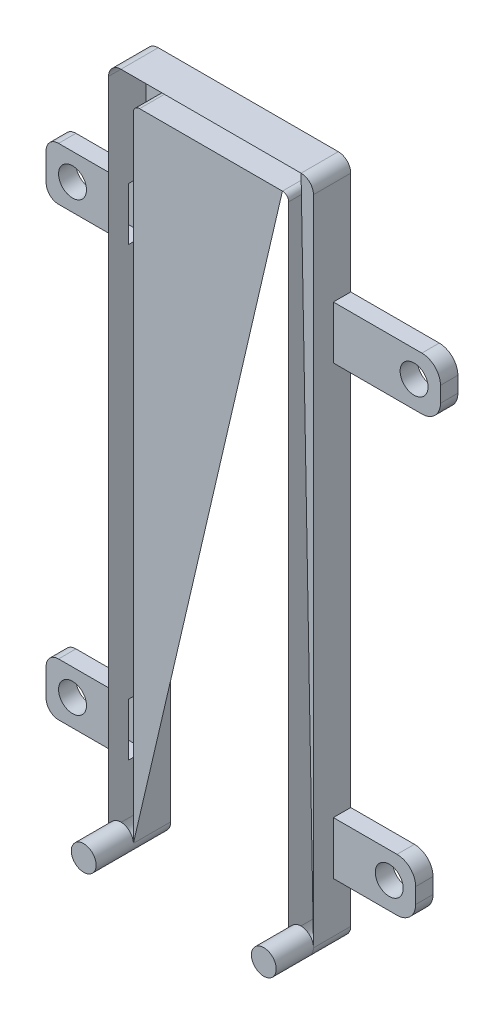
SolidWorks part; units mm, degrees
ref_plane "Přední rovina" through (0, 0, 0) normal (0, 0, 1) x (1, 0, 0)
ref_plane "Horní rovina" through (0, 0, 0) normal (0, 1, 0) x (1, 0, 0)
ref_plane "Pravá rovina" through (0, 0, 0) normal (1, 0, 0) x (0, 0, -1)
sketch "Skica1" plane through (0, 0, 0) normal (0, 0, 1) x (1, 0, 0)
  line L2 (-4, 1.9266) -> (-4, 106.9633)
  line L3 (-2, 108.9633) -> (27, 108.9633)
  line L4 (29, 1.9266) -> (29, 106.9633)
  line L7 (0.9993, 104.9633) -> (24, 104.9633)
  line L9 (-4, 10) -> (-15.25, 10)
  line L10 (-4, 10) -> (-4, 18.5)
  line L11 (-4, 18.5) -> (-15.25, 18.5)
  line L12 (-17.25, 12) -> (-17.25, 16.5)
  line L13 (-4, 81.9) -> (-15.25, 81.9)
  line L14 (-4, 81.9) -> (-4, 90.4)
  line L15 (-4, 90.4) -> (-15.25, 90.4)
  line L16 (-17.25, 83.9) -> (-17.25, 88.4)
  line L17 (29, 90.4) -> (43.25, 90.4)
  line L18 (29, 90.4) -> (29, 81.9)
  line L19 (29, 81.9) -> (43.25, 81.9)
  line L20 (46.25, 87.4) -> (46.25, 84.9)
  line L21 (29, 18.5) -> (39.25, 18.5)
  line L22 (29, 18.5) -> (29, 10)
  line L23 (29, 10) -> (39.25, 10)
  line L24 (42.25, 15.5) -> (42.25, 13)
  line L26 (25, 103.9633) -> (25, 2)
  line L27 (0, 2) -> (0, 104)
  circle A0 centre (-13, 14.25) radius 2.25
  circle A1 centre (-13, 86.15) radius 2.25
  arc A4 (29, 106.9633) -> (27, 108.9633) centre (27, 106.9633) ccw
  arc A5 (-2, 108.9633) -> (-4, 106.9633) centre (-2, 106.9633) ccw
  arc A6 (-17.25, 12) -> (-15.25, 10) centre (-15.25, 12) ccw
  arc A7 (-17.25, 16.5) -> (-15.25, 18.5) centre (-15.25, 16.5) cw
  arc A8 (-17.25, 83.9) -> (-15.25, 81.9) centre (-15.25, 83.9) ccw
  arc A9 (-17.25, 88.4) -> (-15.25, 90.4) centre (-15.25, 88.4) cw
  circle A10 centre (42, 86.15) radius 2.25
  circle A11 centre (38, 14.25) radius 2.25
  arc A12 (43.25, 90.4) -> (46.25, 87.4) centre (43.25, 87.4) cw
  arc A13 (43.25, 81.9) -> (46.25, 84.9) centre (43.25, 84.9) ccw
  arc A14 (39.25, 18.5) -> (42.25, 15.5) centre (39.25, 15.5) cw
  arc A15 (39.25, 10) -> (42.25, 13) centre (39.25, 13) ccw
  arc A16 (24, 104.9633) -> (25, 103.9633) centre (24, 103.9633) cw
  arc A17 (0, 104) -> (0.9993, 104.9633) centre (0.9993, 103.9633) cw
  arc A18 (-4, 1.9266) -> (0, 2) centre (-2, 1.9633) ccw
  arc A19 (25, 2) -> (29, 1.9266) centre (27, 1.9633) ccw
  point P15 (0, 2)
  point P22 (26.9633, -0.0367)
  point P24 (0, 0)
  point P25 (-1.9633, -0.0367)
  point P27 (29.2, 0)
  point P32 (-4, 108.9633)
  point P53 (-9.625, 10)
  point P66 (25, 2)
  dimension "D7" = 4.25
  dimension "D8" = 4.25
  dimension "D11" = 71.9
  dimension "D15" = 9
  dimension "D16" = 109
  dimension "D18" = 4.25
  dimension "D23" = 4.5
  dimension "D24" = 3
  dimension "D25" = 1
  dimension "D26" = 71.9
  dimension "D3" = 4
  dimension "D4" = 25
  dimension "D5" = 4
  dimension "D6" = 51
  dimension "D9" = 9
  dimension "D10" = 4.25
  dimension "D12" = 4.25
  dimension "D13" = 4.25
  dimension "D14" = 4.25
  dimension "D17" = 4.25
  dimension "D19" = 4.25
  dimension "D20" = 4.25
  dimension "D21" = 109
  dimension "D22" = 0
extrude "Přidat vysunutím10" add sketch "Skica1" along normal blind 2.8 contours A9 L16 A8 L13 L2 L15 A1 | L19 A13 L20 A12 L17 L4 A10 | L23 A15 L24 A14 L21 L4 A11 | A7 L12 A6 L9 L2 L11 A0 region at (-10.1158, 14.25, 0) region at (-10.1158, 86.15, 0) region at (34.9705, 14.25, 0) region at (36.8343, 86.15, 0)
extrude "Přidat vysunutím11" add sketch "Skica1<20>" along normal blind 6 contours L26 A19 L4 A4 L3 A5 L2 A18 L27 A17 L7 A16 region at (-2.8611, 5.9633, 0)
sketch "Skica1<20>" plane through (0, 0, 0) normal (0, 0, 1) x (1, 0, 0) same geometry as "Skica1"
sketch "Skica8" plane through (0, 0, 6) normal (0, 0, 1) x (1, 0, 0)
  circle A0 centre (-2, 1.9633) radius 2.0003
  circle A1 centre (27, 1.9633) radius 2
extrude "Přidat vysunutím12" add sketch "Skica8" along normal blind 6
